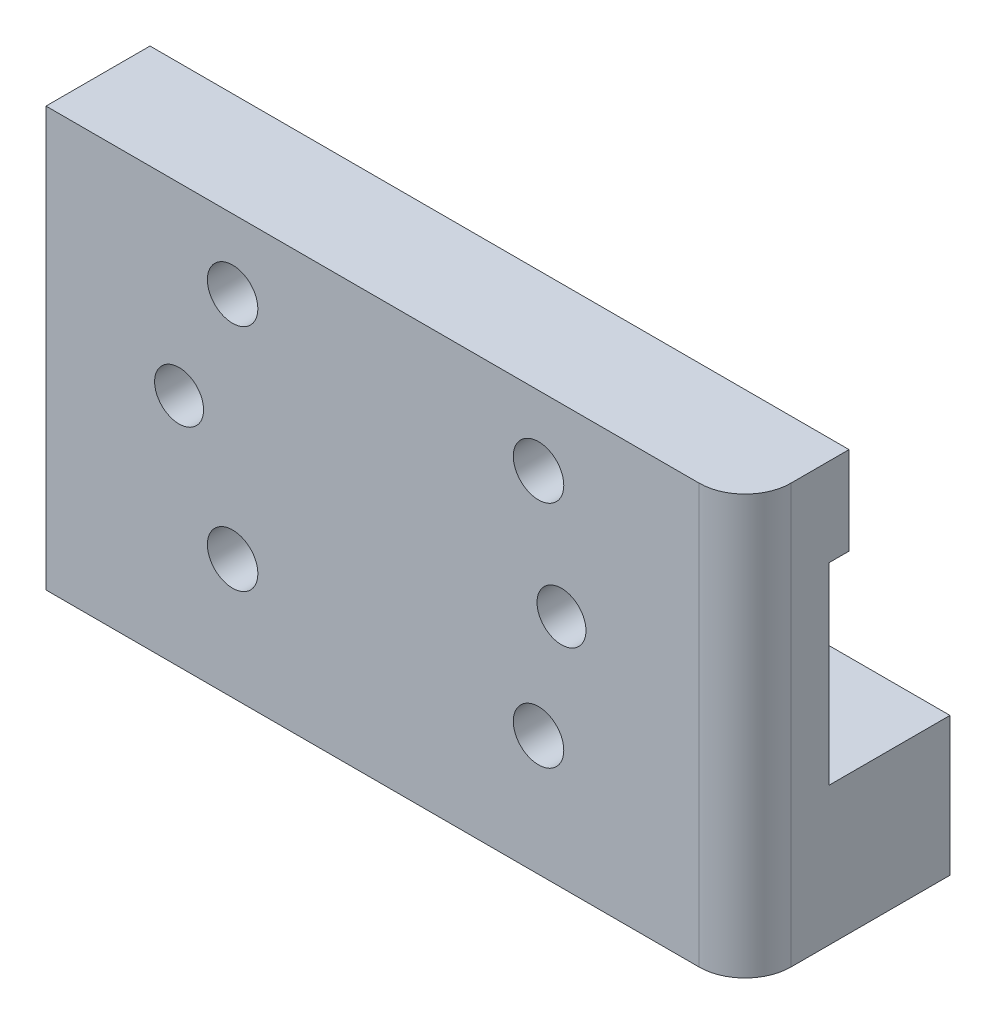
SolidWorks part; units mm, degrees
note: The reader was unsure of these and kept them because the rebuilt part matched: shared geometry of "Croquis1<3>".
ref_plane "Front Plane" through (0, 0, 0) normal (0, 0, 1) x (1, 0, 0)
ref_plane "Top Plane" through (0, 0, 0) normal (0, 1, 0) x (1, 0, 0)
ref_plane "Right Plane" through (0, 0, 0) normal (1, 0, 0) x (0, 0, -1)
sketch "Croquis1" plane through (0, 0, 0) normal (0, 0, 1) x (1, 0, 0)
  line L0 (-59.65, -9.05) -> (-59.65, -3) construction
  line L1 (-105.35, -9.05) -> (-59.65, -9.05)
  line L2 (-105.35, -9.05) -> (-105.35, -3.3)
  line L3 (-105.35, -3.3) -> (-59.65, -3.3)
  line L4 (-59.65, -9.05) -> (-59.65, -3.3)
  line L5 (-105.1213, -3) -> (-59.65, -3) construction
  line L6 (-59.65, -30.7) -> (-59.65, -9.05) construction
  line L7 (-105.35, -30.7) -> (-59.65, -30.7)
  line L8 (-105.35, -30.7) -> (-105.35, -21.65)
  line L9 (-105.35, -21.65) -> (-59.65, -21.65)
  line L10 (-59.65, -30.7) -> (-59.65, -21.65)
  line L11 (-59.65, -30.7) -> (-107.65, -30.7) construction
  line L14 (-105.65, -9.05) -> (-105.65, -3) construction
  circle A1 centre (-93.15, -7.85) radius 1.65
  circle A2 centre (-73.15, -7.85) radius 1.65
  circle A3 centre (-93.15, -22.85) radius 1.65
  circle A4 centre (-73.15, -22.85) radius 1.65
  dimension "D3" = 3.3
  dimension "D1" = 0.3
  dimension "D2" = 12.6
  dimension "D4" = 0.3
extrude "Saliente-Extruir1" add sketch "Croquis1" along normal blind 1.3 from offset 0.1 contours A2 L1 L4 L3 L2 A1
extrude "Saliente-Extruir2" add sketch "Croquis1<3>" against normal offset from surface 0.1 and the other way blind 1.3 from offset 0.1 separate body contours A4 L9 A3 L8 L7 L10
sketch "Croquis1<3>" plane through (0, 0, 0) normal (0, 0, 1) x (1, 0, 0) same geometry as "Croquis1"
sketch "Croquis2" plane through (0, 0, 1.4) normal (0, 0, 1) x (1, 0, 0)
  line L1 (-105.35, -3.3) -> (-59.65, -3.3)
  line L2 (-105.35, -3.3) -> (-105.35, -30.7)
  line L3 (-105.35, -30.7) -> (-59.65, -30.7)
  line L4 (-59.65, -3.3) -> (-59.65, -30.7)
  circle A0 centre (-93.15, -7.85) radius 1.65 construction
  circle A1 centre (-93.15, -7.85) radius 1.65
  circle A2 centre (-73.15, -7.85) radius 1.65 construction
  circle A3 centre (-73.15, -7.85) radius 1.65
  circle A4 centre (-93.15, -22.85) radius 1.65 construction
  circle A5 centre (-93.15, -22.85) radius 1.65
  circle A6 centre (-73.15, -22.85) radius 1.65 construction
  circle A7 centre (-73.15, -22.85) radius 1.65
  circle A8 centre (-96.65, -15.35) radius 1.6 construction
  circle A9 centre (-96.65, -15.35) radius 1.6
  circle A10 centre (-71.65, -15.35) radius 1.6 construction
  circle A11 centre (-71.65, -15.35) radius 1.6
extrude "Saliente-Extruir3" add sketch "Croquis2" along normal blind 5.5
fillet "Redondeo1" radius 3 1 edges at (-59.65, -17, 6.9)
